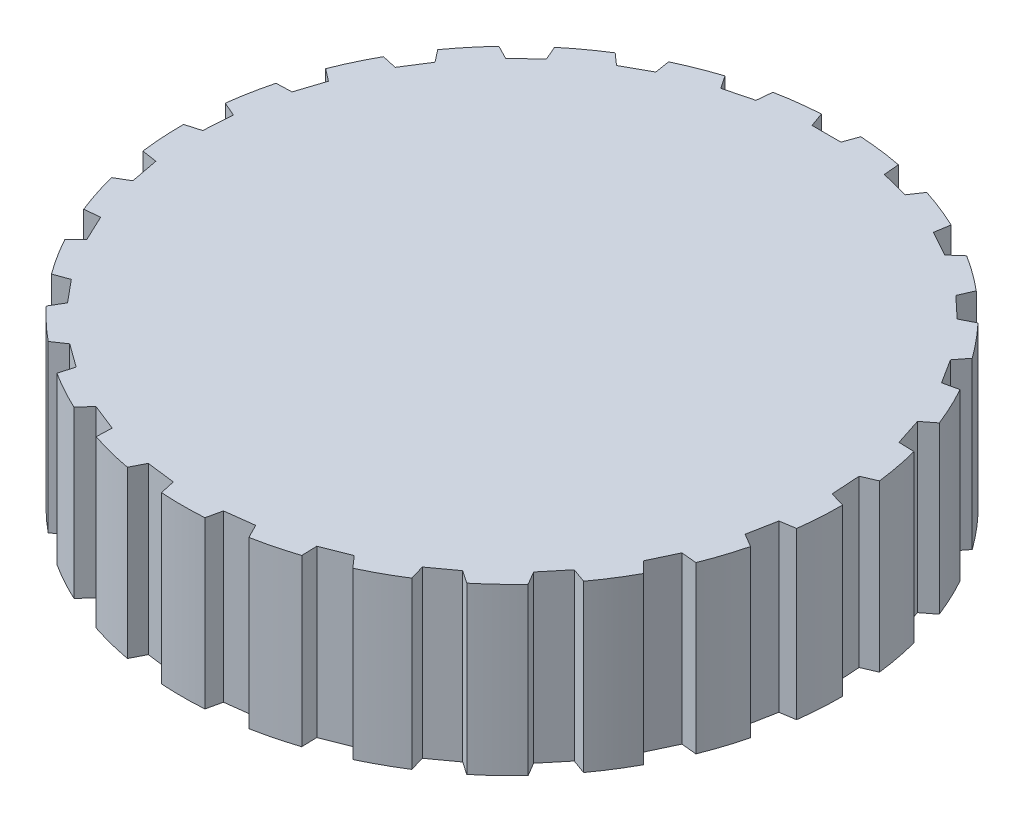
SolidWorks part; units mm, degrees
ref_plane "Front Plane" through (0, 0, 0) normal (0, 0, 1) x (1, 0, 0)
ref_plane "Top Plane" through (0, 0, 0) normal (0, 1, 0) x (1, 0, 0)
ref_plane "Right Plane" through (0, 0, 0) normal (1, 0, 0) x (0, 0, -1)
sketch "Sketch5" plane through (0, 0, 0) normal (0, 1, 0) x (1, 0, 0)
  circle A0 centre (0, 0) radius 37.8968
extrude "Boss-Extrude2" add sketch "Sketch5" along normal blind 19.05
sketch "Sketch8" plane through (0, 19.05, 0) normal (0, 1, 0) x (1, 0, 0)
  line L0 (0, 38.1) -> (2.36, 38.1)
  line L1 (0, 38.1) -> (-2.36, 38.1)
  line L5 (0, 36.15) -> (-1.66, 36.15)
  line L6 (0, 36.15) -> (1.66, 36.15)
  line L7 (-2.36, 38.1) -> (-1.66, 36.15)
  line L8 (2.36, 38.1) -> (1.66, 36.15)
  point P0 (0, 38.1)
  dimension "D1" = 1.66
  dimension "D2" = 1.66
  dimension "D3" = 1.95
  dimension "D4" = 2.36
  dimension "D5" = 2.36
extrude "Cut-Extrude1" cut sketch "Sketch8" against normal blind 22.05
pattern_circular "CirPattern1" count 25 over 360 about axis through (0, 19.05, 0) along (0, 1, 0) of "Cut-Extrude1"
sketch "Sketch9" plane through (0, 19.05, 0) normal (0, 1, 0) x (1, 0, 0)
  line L0 (0, 7.25) -> (2.6, 7.25)
  line L1 (0, 7.25) -> (-2.6, 7.25)
  line L2 (-2.6, 7.25) -> (-2.6, 6.7678)
  line L3 (2.6, 7.25) -> (2.6, 6.7678)
  line L4 (-2.6, 7.25) -> (-2.6, 9.75)
  line L5 (-2.6, 9.75) -> (2.6, 9.75)
  line L6 (2.6, 9.75) -> (2.6, 7.25)
  circle A0 centre (0, 0) radius 7.25
extrude "Cut-Extrude2" [suppressed] cut sketch "Sketch9" against normal blind 25.4 contours A0 | L6 L5 L4 L1 L0 | A0 L1 L2 | A0 L3 L0
